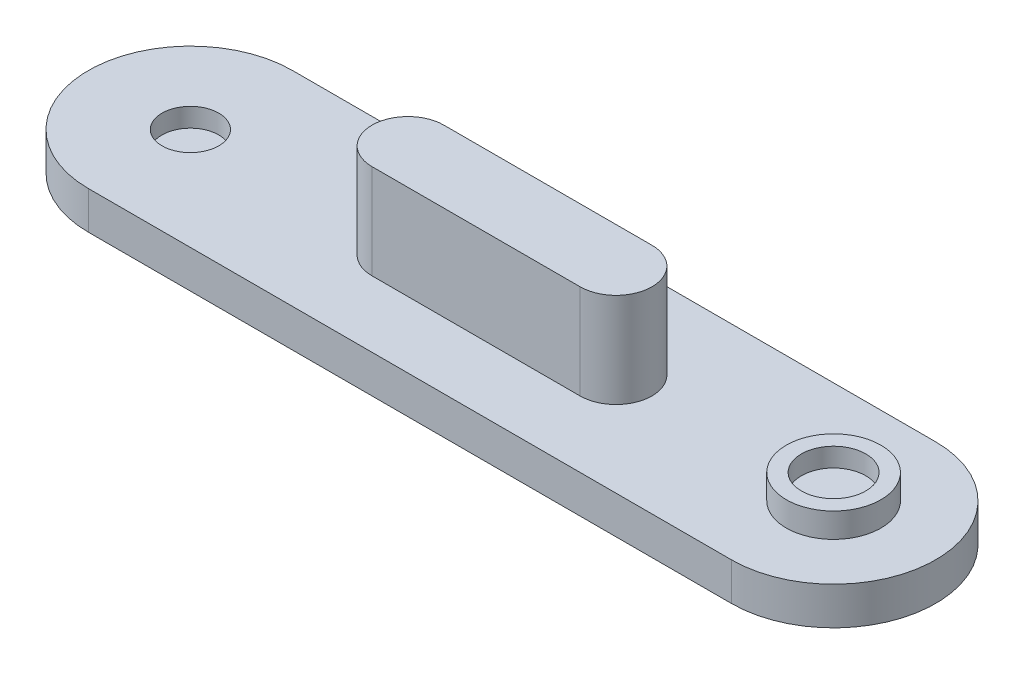
SolidWorks part; units mm, degrees
ref_plane "Front Plane" through (0, 0, 0) normal (0, 0, 1) x (1, 0, 0)
ref_plane "Top Plane" through (0, 0, 0) normal (0, 1, 0) x (1, 0, 0)
ref_plane "Right Plane" through (0, 0, 0) normal (1, 0, 0) x (0, 0, -1)
sketch "Sketch1" plane through (0, 0, 0) normal (0, 1, 0) x (1, 0, 0)
  line L0 (-142.4958, 0) -> (136.0591, 0) construction
  line L1 (0, 82.9006) -> (0, -67.1417) construction
  line L2 (-42.5, -13.5) -> (42.5, -13.5)
  line L3 (-42.5, 13.5) -> (42.5, 13.5)
  arc A0 (-42.5, 13.5) -> (-42.5, -13.5) centre (-42.5, 0) ccw
  arc A1 (42.5, 13.5) -> (42.5, -13.5) centre (42.5, 0) cw
  dimension "D1" = 85
  dimension "D2" = 27
extrude "Boss-Extrude1" add sketch "Sketch1" along normal blind 5
sketch "Sketch2" plane through (0, 5, 0) normal (0, 1, 0) x (1, 0, 0)
  circle A0 centre (-42.5, 0) radius 3.75
  arc A1 (-42.5, 13.5) -> (-42.5, -13.5) centre (-42.5, 0) ccw construction
  dimension "D1" = 7.5
extrude "Cut-Extrude1" cut sketch "Sketch2" against normal blind 2.5
sketch "Sketch3" plane through (0, 5, 0) normal (0, 1, 0) x (1, 0, 0)
  circle A0 centre (42.5, 0) radius 6.25
  arc A1 (42.5, -13.5) -> (42.5, 13.5) centre (42.5, 0) ccw construction
  dimension "D1" = 12.5
extrude "Boss-Extrude3" add sketch "Sketch3" along normal blind 3.25
sketch "Sketch4" plane through (0, 8.25, 0) normal (0, 1, 0) x (1, 0, 0)
  circle A0 centre (42.5, 0) radius 4.25
  circle A1 centre (42.5, 0) radius 6.25 construction
  dimension "D1" = 8.5
extrude "Cut-Extrude2" cut sketch "Sketch4" against normal blind 2.5
sketch "Sketch5" plane through (0, 5, 0) normal (0, 1, 0) x (1, 0, 0)
  line L0 (0, 28.1167) -> (0, -35.5844) construction
  line L1 (-13.75, 4.75) -> (13.75, 4.75)
  line L2 (-13.75, -4.75) -> (13.75, -4.75)
  arc A0 (-13.75, 4.75) -> (-13.75, -4.75) centre (-13.75, 0) ccw
  arc A1 (13.75, 4.75) -> (13.75, -4.75) centre (13.75, 0) cw
  dimension "D1" = 27.5
  dimension "D2" = 9.5
extrude "Boss-Extrude4" add sketch "Sketch5" along normal blind 12.5
